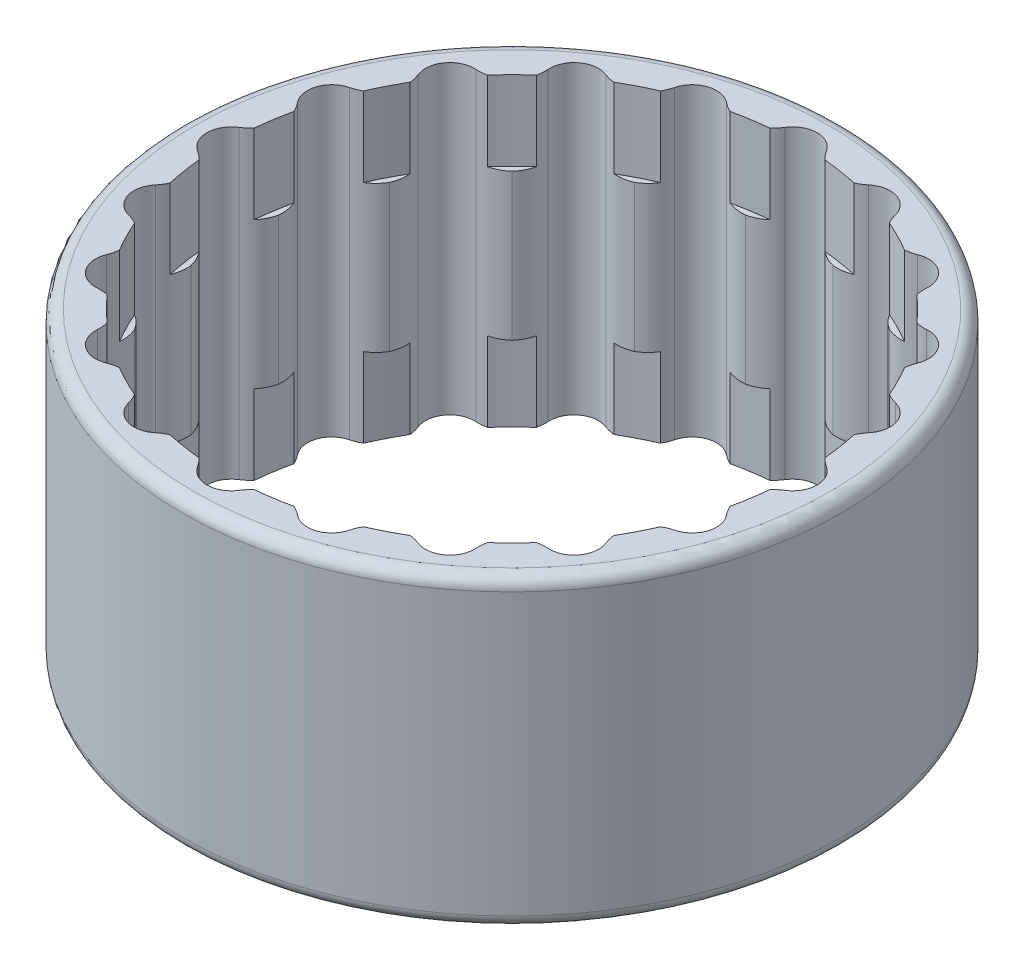
SolidWorks part; units mm, degrees
ref_plane "Front Plane" through (0, 0, 0) normal (0, 0, 1) x (1, 0, 0)
ref_plane "Top Plane" through (0, 0, 0) normal (0, 1, 0) x (1, 0, 0)
ref_plane "Right Plane" through (0, 0, 0) normal (1, 0, 0) x (0, 0, -1)
sketch "Sketch1" plane through (0, 0, 0) normal (0, 1, 0) x (1, 0, 0)
  circle A0 centre (0, 0) radius 27
  dimension "D1" = 54
extrude "Boss-Extrude1" add sketch "Sketch1" along normal blind 25
sketch "Sketch3" plane through (0, 25, 0) normal (0, 1, 0) x (1, 0, 0)
  circle A0 centre (0, 0) radius 23.5
  dimension "D1" = 47
extrude "Cut-Extrude1" cut sketch "Sketch3" against normal blind 6.5
sketch "Sketch4" plane through (0, 0, 0) normal (0, -1, 0) x (1, 0, 0)
  circle A0 centre (0, 0) radius 23.5
  dimension "D1" = 47
extrude "Cut-Extrude2" cut sketch "Sketch4" against normal blind 6.5
sketch "Sketch5" plane through (0, 18.5, 0) normal (0, 1, 0) x (1, 0, 0)
  circle A0 centre (0, 0) radius 23
  dimension "D1" = 46
extrude "Cut-Extrude4" cut sketch "Sketch5" against normal through all
sketch "Sketch6" plane through (0, 18.5, 0) normal (0, 1, 0) x (1, 0, 0)
  circle A0 centre (0, 0) radius 23 construction
  circle A1 centre (0, 23) radius 2
  circle A2 centre (7.1074, 21.8743) radius 2
  circle A3 centre (13.5191, 18.6074) radius 2
  circle A4 centre (18.6074, 13.5191) radius 2
  circle A5 centre (21.8743, 7.1074) radius 2
  circle A6 centre (23, 0) radius 2
  circle A7 centre (21.8743, -7.1074) radius 2
  circle A8 centre (18.6074, -13.5191) radius 2
  circle A9 centre (13.5191, -18.6074) radius 2
  circle A10 centre (7.1074, -21.8743) radius 2
  circle A11 centre (0, -23) radius 2
  circle A12 centre (-7.1074, -21.8743) radius 2
  circle A13 centre (-13.5191, -18.6074) radius 2
  circle A14 centre (-18.6074, -13.5191) radius 2
  circle A15 centre (-21.8743, -7.1074) radius 2
  circle A16 centre (-23, 0) radius 2
  circle A17 centre (-21.8743, 7.1074) radius 2
  circle A18 centre (-18.6074, 13.5191) radius 2
  circle A19 centre (-13.5191, 18.6074) radius 2
  circle A20 centre (-7.1074, 21.8743) radius 2
  point P45 (0, 0)
  dimension "D1" = 46
  dimension "D2" = 4
  dimension "D3" = 20
extrude "Cut-Extrude5" cut sketch "Sketch6" against normal through all both and the other way through all
fillet "Fillet1" radius 3 40 edges at (21.1741, 12.5, -8.9808) (19.7115, 12.5, -11.8514) (22.409, 12.5, -5.1802) (22.913, 12.5, -1.9981) (22.913, 12.5, 1.9981) (22.409, 12.5, 5.1802) (21.1741, 12.5, 8.9808) (19.7115, 12.5, 11.8514) (15.0845, 12.5, -17.3626) (17.3626, 12.5, -15.0845) (11.8514, 12.5, -19.7115) (8.9808, 12.5, -21.1741) (5.1802, 12.5, -22.409) (1.9981, 12.5, -22.913) (-1.9981, 12.5, -22.913) (-5.1802, 12.5, -22.409) (-8.9808, 12.5, -21.1741) (-11.8514, 12.5, -19.7115) (-15.0845, 12.5, -17.3626) (-17.3626, 12.5, -15.0845) (-19.7115, 12.5, -11.8514) (-21.1741, 12.5, -8.9808) (-22.409, 12.5, -5.1802) (-22.913, 12.5, -1.9981) (-22.913, 12.5, 1.9981) (-22.409, 12.5, 5.1802) (-21.1741, 12.5, 8.9808) (-19.7115, 12.5, 11.8514) (-17.3626, 12.5, 15.0845) (-15.0845, 12.5, 17.3626) (-11.8514, 12.5, 19.7115) (-8.9808, 12.5, 21.1741) (-5.1802, 12.5, 22.409) (-1.9981, 12.5, 22.913) (1.9981, 12.5, 22.913) (5.1802, 12.5, 22.409) (8.9808, 12.5, 21.1741) (11.8514, 12.5, 19.7115) (15.0845, 12.5, 17.3626) (17.3626, 12.5, 15.0845)
fillet "Fillet2" radius 1 2 edges at (0, 0, 27) (0, 25, 27)
